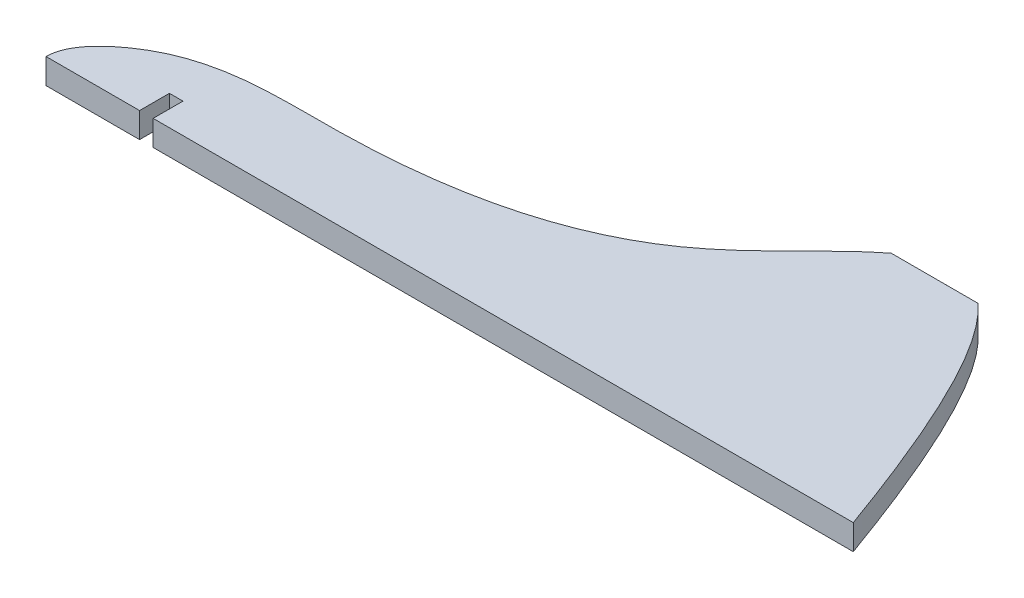
SolidWorks part; units mm, degrees
ref_plane "Front Plane" through (0, 0, 0) normal (0, 0, 1) x (1, 0, 0)
ref_plane "Top Plane" through (0, 0, 0) normal (0, 1, 0) x (1, 0, 0)
ref_plane "Right Plane" through (0, 0, 0) normal (1, 0, 0) x (0, 0, -1)
sketch "Sketch1" plane through (0, 0, 0) normal (0, 1, 0) x (1, 0, 0)
  line L2 (0, 0) -> (203.2, 0)
  line L3 (0, 0) -> (0, -63.5)
  line L4 (0, -63.5) -> (203.2, -63.5)
  line L5 (203.2, 0) -> (203.2, -63.5)
  line L6 (23.5525, -63.5) -> (26.9641, -63.5)
  line L7 (23.5525, -63.5) -> (23.5525, -55.989)
  line L8 (23.5525, -55.989) -> (26.9641, -55.989)
  line L9 (26.9641, -63.5) -> (26.9641, -55.989)
  spline S0 degree 3 poles (0, -63.5) (-0.0049, -58.9051) (15.7354, -41.5353) (66.471, -45.5603) (146.4102, -28.5646) (164.4467, 43.7689) (203.2, -63.5) knots 0 0 0 0 0.046675 0.207236 0.499057 1 1 1 1
  dimension "D1" = 63.5
  dimension "D2" = 203.2
extrude "Boss-Extrude1" add sketch "Sketch1" along normal blind 6.35 contours S0 L4 L7 L8 L9 L2 region at (123.3367, 0, 42.4033)
